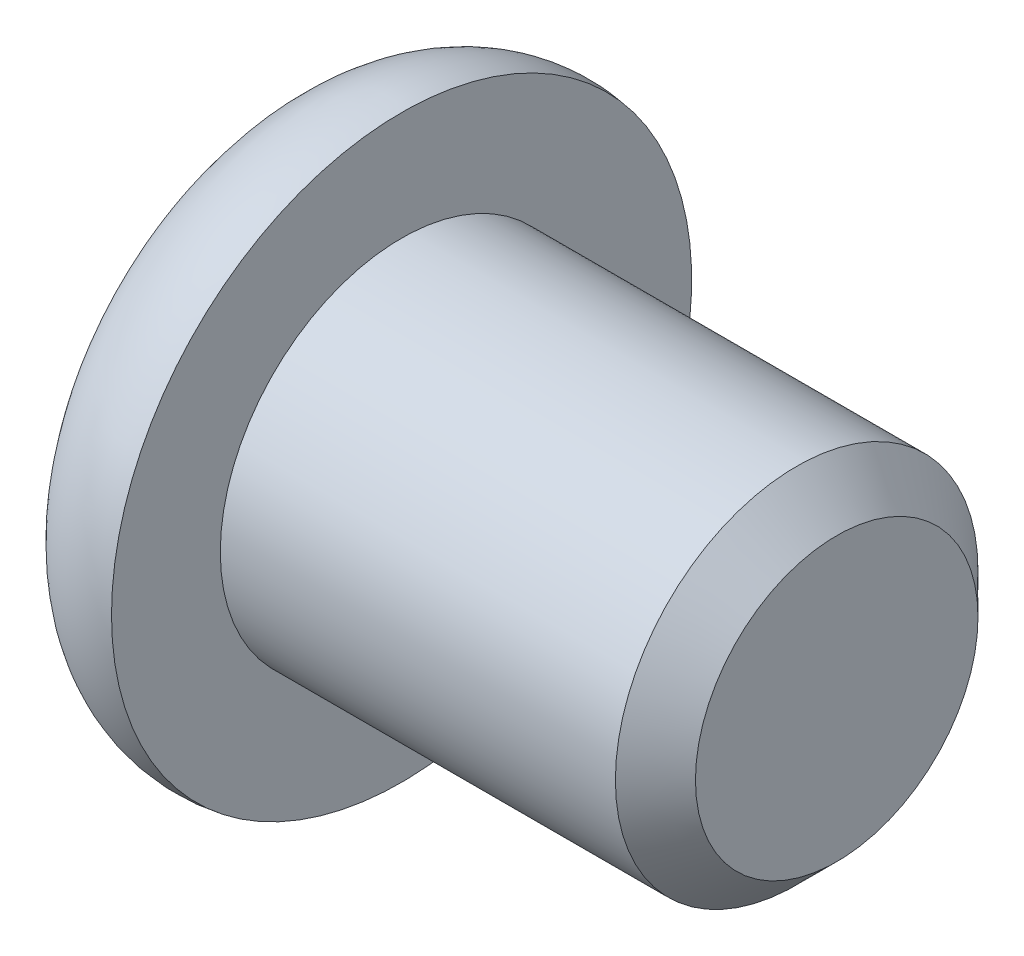
SolidWorks part; units mm, degrees
ref_plane "Front Plane" through (0, 0, 0) normal (0, 0, 1) x (1, 0, 0)
ref_plane "Top Plane" through (0, 0, 0) normal (0, 1, 0) x (1, 0, 0)
ref_plane "Right Plane" through (0, 0, 0) normal (1, 0, 0) x (0, 0, -1)
ref_plane "Plane1" through (0, 0, 0) normal (0, 0, 1) x (1, 0, 0)
sketch "Sketch1" plane through (0, 0, 0) normal (0, 0, 1) x (1, 0, 0)
  line L0 (-0.8, 0) -> (-0.8, 1.6)
  line L1 (0, 2) -> (0, 1.25)
  line L2 (0, 1.25) -> (2.724, 1.25)
  line L3 (2.724, 1.25) -> (3, 0.974)
  line L4 (3, 0.974) -> (3, 0)
  line L5 (3, 0) -> (-0.8, 0)
  line L6 (3, 0) -> (-0.8, 0) construction
  arc A0 (-0.8, 1.6) -> (0, 2) centre (-0.1307, 1.2615) cw
revolve "Revolve1" add sketch "Sketch1" angle 360 about L6 reverse direction yes
cosmetic thread "Cosmetic Thread1" parameters "D1"=2.522, "D2"=1.948
ref_plane "Plane2" through (0, 0, 0) normal (0, 0, 1) x (1, 0, 0)
sketch "Sketch2" plane through (0, 0, 0) normal (0, 0, 1) x (1, 0, 0)
  line L0 (-0.8, -1.2) -> (0.4, -0.6)
  line L1 (0.4, -0.6) -> (0.6, 0)
  line L2 (0.6, 0) -> (0.4, 0.6)
  line L3 (0.4, 0.6) -> (-0.8, 1.2)
  line L4 (-0.8, 1.2) -> (-0.8, -1.2)
extrude "Cut-Extrude1" cut sketch "Sketch2" against normal blind 0.2 and the other way blind 0.2
ref_plane "Plane3" through (0, 0, 0) normal (0, 1, 0) x (1, 0, 0)
sketch "Sketch3" plane through (0, 0, 0) normal (0, 1, 0) x (1, 0, 0)
  line L0 (-0.8, -1.2) -> (0.4, -0.6)
  line L1 (0.4, -0.6) -> (0.6, 0)
  line L2 (0.6, 0) -> (0.4, 0.6)
  line L3 (0.4, 0.6) -> (-0.8, 1.2)
  line L4 (-0.8, 1.2) -> (-0.8, -1.2)
extrude "Cut-Extrude2" cut sketch "Sketch3" against normal blind 0.2 and the other way blind 0.2
